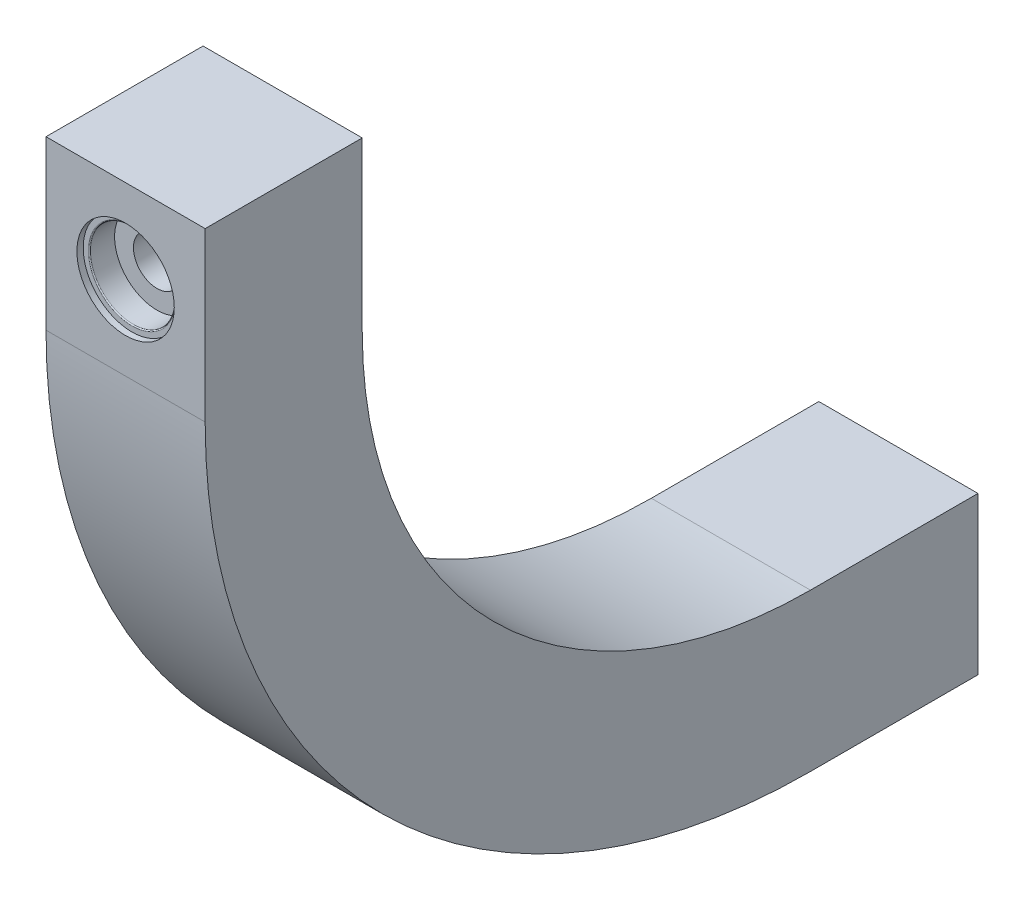
SolidWorks part; units mm, degrees
ref_plane "Front Plane" through (0, 0, 0) normal (0, 0, 1) x (1, 0, 0)
ref_plane "Top Plane" through (0, 0, 0) normal (0, 1, 0) x (1, 0, 0)
ref_plane "Right Plane" through (0, 0, 0) normal (1, 0, 0) x (0, 0, -1)
ref_axis "Z" through (0, 0, 109.5585) along (0, 0, -1)
ref_axis "X" through (8.36, 0, 0) along (-1, 0, 0)
sketch "Sketch4" plane through (0, 0, 0) normal (0, 0, 1) x (1, 0, 0)
  circle A0 centre (0, 0) radius 49.8046 construction
  dimension "D1" = 99.6092
sketch "Sketch5" plane through (0, 0, 0) normal (1, 0, 0) x (0, 0, -1)
  line L0 (-50.8046, 8) -> (-50.8046, 0)
  line L1 (-50.8046, 0) -> (-50.8046, -8)
  line L2 (-65.8046, -8) -> (-65.8046, 8)
  line L6 (-65.8046, 8) -> (-50.8046, 8)
  line L12 (-109.5585, 0) -> (-13.0351, 0) construction
  line L13 (0, 0) -> (-14.9091, -14.9091) construction
  line L14 (0, 0) -> (7.0065, 0) construction
  line L15 (0, -50.8046) -> (-8, -50.8046)
  line L16 (8, -50.8046) -> (0, -50.8046)
  line L17 (-8, -65.8046) -> (8, -65.8046)
  line L18 (8, -65.8046) -> (8, -50.8046)
  circle A0 centre (0, 0) radius 14 construction
  arc A1 (-50.8046, -8) -> (-8, -50.8046) centre (-8, -8) ccw
  arc A2 (-65.8046, -8) -> (-8, -65.8046) centre (-8, -8) ccw
  point P2 (9.4307, -21)
  point P4 (0, -2.1363)
  dimension "D1" = 28
  dimension "D4" = 8
  dimension "D2" = 45
  dimension "D3" = 15
  dimension "D5" = 50.8046
sketch "Sketch6" plane through (0, 0, 0) normal (0, 1, 0) x (1, 0, 0)
  circle A0 centre (0, 0) radius 49.8046 construction
  dimension "D1" = 99.6092
extrude "Boss-Extrude1" add sketch "Sketch5" along normal blind 7.6 and the other way blind 7.6
sketch "Sketch7" plane through (0, 0, 0) normal (0, 0, 1) x (1, 0, 0)
  circle A0 centre (0, 0) radius 2.25
  dimension "D1" = 4.5
extrude "Cut-Extrude1" cut sketch "Sketch7" along normal through all
ref_axis "Y" through (0, -9.3489, 0) along (0, -1, 0)
sketch "Sketch16" plane through (0, 0, 0) normal (1, 0, 0) x (0, 0, -1)
  line L0 (0, -66.8046) -> (0, 0) construction
  dimension "D1" = 66.8046
ref_plane "Plane1" through (0, -66.8046, 0) normal (0, 1, 0) x (1, 0, 0)
ref_axis "CX" through (0, -66.8046, 4.4) along (0, 0, -1)
ref_plane "Plane2" through (0, 0, 0) normal (0, 0, -1) x (0, 1, 0)
ref_plane "Plane3" through (0, 0, 0) normal (1, 0, 0) x (0, 0, -1)
ref_axis "CZ" through (0, -8.7018, 0) along (0, -1, 0)
ref_axis "CY" through (-0.6471, -66.8046, 0) along (1, 0, 0)
ref_point "CO"
sketch "Sketch15" plane through (0, -65.8046, 0) normal (0, -1, 0) x (1, 0, 0)
  circle A0 centre (0, 0) radius 2
  dimension "D1" = 4
extrude "Cut-Extrude11" cut sketch "Sketch15" against normal blind 10
sketch "Sketch18" plane through (0, 0, 0) normal (1, 0, 0) x (0, 0, -1)
  line L0 (-65.8046, 4.65) -> (-65.8046, 0)
  line L1 (-65.8046, 0) -> (-62.8046, 0)
  line L2 (-62.8046, 0) -> (-62.8046, 4.05)
  line L3 (-62.8046, 4.05) -> (-65.1046, 4.05)
  line L4 (-65.2046, 4.15) -> (-65.2046, 4.65)
  line L5 (-65.2046, 4.65) -> (-65.8046, 4.65)
  line L6 (-68.6876, 0) -> (-58.3046, 0) construction
  line L7 (-58.3046, 0) -> (-58.3046, 8) construction
  line L8 (-51.4046, 4.65) -> (-50.8046, 4.65)
  line L9 (-51.4046, 4.15) -> (-51.4046, 4.65)
  line L10 (-53.8046, 4.05) -> (-51.5046, 4.05)
  line L11 (-53.8046, 0) -> (-53.8046, 4.05)
  line L12 (-50.8046, 0) -> (-53.8046, 0)
  line L13 (-50.8046, 4.65) -> (-50.8046, 0)
  line L14 (-109.5585, 0) -> (-13.0351, 0) construction
  line L15 (-65.8046, 8) -> (-50.8046, 8) construction
  line L16 (-65.8046, -8) -> (-65.8046, 8) construction
  arc A0 (-65.1046, 4.05) -> (-65.2046, 4.15) centre (-65.1046, 4.15) cw
  arc A1 (-51.5046, 4.05) -> (-51.4046, 4.15) centre (-51.5046, 4.15) ccw
  point P23 (-65.2046, 4.05)
  point P26 (-51.4046, 4.05)
  dimension "D5" = 0.1
  dimension "D6" = 0.1
  dimension "D1" = 0.6
  dimension "D2" = 8.1
  dimension "D3" = 3
  dimension "D4" = 4.65
revolve "Cut-Revolve1" cut sketch "Sketch18" angle 360 about axis through (0, 0, 109.5585) along (0, 0, -1)
equation "\"rbracket-width\"= \"L2Thickness\" + 0.2"
equation "\"EyeCaptureRadius\"= ( \"EyeDiameter\" + \"EyeClearance\" ) / 2"
equation "\"rbracket_planetocenterline_dist\"= \"BasePlaneDistance\""
equation "\"EyeDiameter\" = 99.60916292"
equation "\"BasePlaneDistance\" = \"EyeDiameter\"/2+\"L2Thickness\"+\"EyeClearance\""
equation "\"EyeClearance\" = 2"
equation "\"D1@Sketch4\"=\"EyeDiameter\""
equation "\"D1@Sketch6\"=\"EyeDiameter\""
equation "\"D1@Boss-Extrude1\"=\"rbracket-width\"/2"
equation "\"D2@Boss-Extrude1\"=\"rbracket-width\"/2"
equation "\"L2Thickness\" = 3.75 * \"shaft_diameter\""
equation "\"D3@Sketch5\"=\"L2Thickness\""
equation "\"D5@Sketch5\"=(\"EyeDiameter\"+\"EyeClearance\")/2"
equation "\"BearingThickness\"= 6"
equation "\"BearingOD\"=4.5"
equation "\"OuterBearingProudDistance\"= 0"
equation "\"FlangeOD\"=7.5"
equation "\"FlangeThickness\"= 0.75"
equation "\"PrinterFilamentThickness\"= 0.1'For setting distances for things like pressfits"
equation "\"ApplyPrinterOffset\"= 1'Set to 0 for line-to-line. Set to 1 for applying guestimate dimensions to make the printer produce good parts"
equation "\"D1@Cut-Extrude11\"=\"shaft_diameter\"*2.5"
equation "\"D1@Sketch16\"=\"BasePlaneDistance\""
equation "\"D2@Sketch18\"=\"ApplyPrinterOffset\"*\"PrinterFilamentThickness\" + 8"
equation "\"D4@Sketch18\"=4.6 + \"ApplyPrinterOffset\"*\"PrinterFilamentThickness\"/2"
equation "\"L2_ID\" = 20"
equation "\"vx\" = 0"
equation "\"vy\" = 0"
equation "\"vz\" = 200"
equation "\"parametric_end\" = 1"
equation "\"Rw_3_xx\" = -(\"vz\")/sqr((\"vx\")^2 + (\"vz\")^2)"
equation "\"Rw_3_xy\" = 0"
equation "\"Rw_3_xz\" = (\"vx\")/sqr((\"vx\")^2 + (\"vz\")^2)"
equation "\"Rw_3_zx\" = (\"vx\")/sqr((\"vx\")^2 + (\"vy\")^2 + (\"vz\")^2)"
equation "\"Rw_3_zy\" = (\"vy\")/sqr((\"vx\")^2 + (\"vy\")^2 + (\"vz\")^2)"
equation "\"Rw_3_zz\" = (\"vz\")/sqr((\"vx\")^2 + (\"vy\")^2 + (\"vz\")^2)"
equation "\"Rw_3_yx\" = (\"vx\")*(\"vy\")/sqr((\"vx\")^4 + (\"vx\")^2*(\"vy\")^2 + 2*(\"vx\")^2*(\"vz\")^2 + (\"vy\")^2*(\"vz\")^2 + (\"vz\")^4)"
equation "\"Rw_3_yy\" = -sqr((\"vx\")^2 + (\"vz\")^2)/sqr((\"vx\")^2 + (\"vy\")^2 + (\"vz\")^2)"
equation "\"Rw_3_yz\" = (\"vy\")*(\"vz\")/sqr((\"vx\")^4 + (\"vx\")^2*(\"vy\")^2 + 2*(\"vx\")^2*(\"vz\")^2 + (\"vy\")^2*(\"vz\")^2 + (\"vz\")^4)"
equation "\"O2Targx\" = -\"BasePlaneDistance\"*(\"vx\")*(\"vy\")/sqr((\"vx\")^4 + (\"vx\")^2*(\"vy\")^2 + 2*(\"vx\")^2*(\"vz\")^2 + (\"vy\")^2*(\"vz\")^2 + (\"vz\")^4)"
equation "\"O2Targy\" = \"BasePlaneDistance\"*sqr((\"vx\")^2 + (\"vz\")^2)/sqr((\"vx\")^2 + (\"vy\")^2 + (\"vz\")^2)"
equation "\"O2Targz\" = -\"BasePlaneDistance\"*(\"vy\")*(\"vz\")/sqr((\"vx\")^4 + (\"vx\")^2*(\"vy\")^2 + 2*(\"vx\")^2*(\"vz\")^2 + (\"vy\")^2*(\"vz\")^2 + (\"vz\")^4)"
equation "\"O2Targx_0\" = -(\"BasePlaneDistance\")*sqr((\"vx\")^2 + (\"vz\")^2)/sqr((\"vx\")^2 + (\"vy\")^2 + (\"vz\")^2)"
equation "\"O2Targy_0\" = -(\"BasePlaneDistance\")*(\"vy\")*(\"vz\")/sqr((\"vx\")^4 + (\"vx\")^2*(\"vy\")^2 + 2*(\"vx\")^2*(\"vz\")^2 + (\"vy\")^2*(\"vz\")^2 + (\"vz\")^4)"
equation "\"O2Targz_0\" = (\"BasePlaneDistance\")*(\"vx\")*(\"vy\")/sqr((\"vx\")^4 + (\"vx\")^2*(\"vy\")^2 + 2*(\"vx\")^2*(\"vz\")^2 + (\"vy\")^2*(\"vz\")^2 + (\"vz\")^4) + (\"BasePlaneDistance\")"
equation "\"theta2_s1\" = arcsin(((\"BasePlaneDistance\") - (\"O2Targz_0\"))/(\"BasePlaneDistance\")) + pi"
equation "\"theta2_s2\" = -arcsin(((\"BasePlaneDistance\") - (\"O2Targz_0\"))/(\"BasePlaneDistance\"))"
equation "\"theta1_s1\" = arcsin((\"O2Targy_0\")/((\"BasePlaneDistance\")*cos((\"Theta2\")))) + pi"
equation "\"theta1_s2\" = -arcsin((\"O2Targy_0\")/((\"BasePlaneDistance\")*cos((\"Theta2\"))))"
equation "\"theta1_s3\" = -arccos(-(\"O2Targx_0\")/((\"BasePlaneDistance\")*cos((\"Theta2\")))) + 2*pi"
equation "\"theta1_s4\" = arccos(-(\"O2Targx_0\")/((\"BasePlaneDistance\")*cos((\"Theta2\"))))"
equation "\"Theta1\" = \"theta1_s2\" 'so far, theta1_s1 and theta1_s4 have agreed, and they agree with the sw constraint solver"
equation "\"Theta2\" = \"theta2_s2\""
equation "\"o2_x\" = -(\"BasePlaneDistance\")*cos((\"Theta1\"))*cos((\"Theta2\"))"
equation "\"o2_y\" = -(\"BasePlaneDistance\")*sin((\"Theta1\"))*cos((\"Theta2\"))"
equation "\"o2_z\" = (\"BasePlaneDistance\")*(sin((\"Theta2\")) + 1)"
equation "\"o1_x\" = (\"BasePlaneDistance\")*sin((\"Theta1\"))"
equation "\"o1_y\" = -(\"BasePlaneDistance\")*cos((\"Theta1\"))"
equation "\"o1_z\" = (\"BasePlaneDistance\")"
equation "\"Actuator1_Theta\" = atn(\"vx\"/\"vz\") 'ik solution for the single link joint"
equation "\"Actuator2_Theta\" = \"Theta1\"  'ik solution for the double link joint"
equation "\"MotorBaseThickness\" = 3 "
equation "\"BaseThickness\" = 3 "
equation "\"EncoderToMagnetAirgap\" = 1 'Encoder to magnet airgap"
equation "\"EncoderHeight\" = 1.192  'Height of the encoder"
equation "\"MagnetThickness\" = 0.5  'Magnet thickness"
equation "\"pcb_thickness\" = 1.6  'Thickness of the PCB"
equation "\"pcb_outer_diameter\" = 32 'the OD of the pcb"
equation "\"shaft_diameter\" = 4"
equation "\"D1@Sketch15\"=\"shaft_diameter\""
